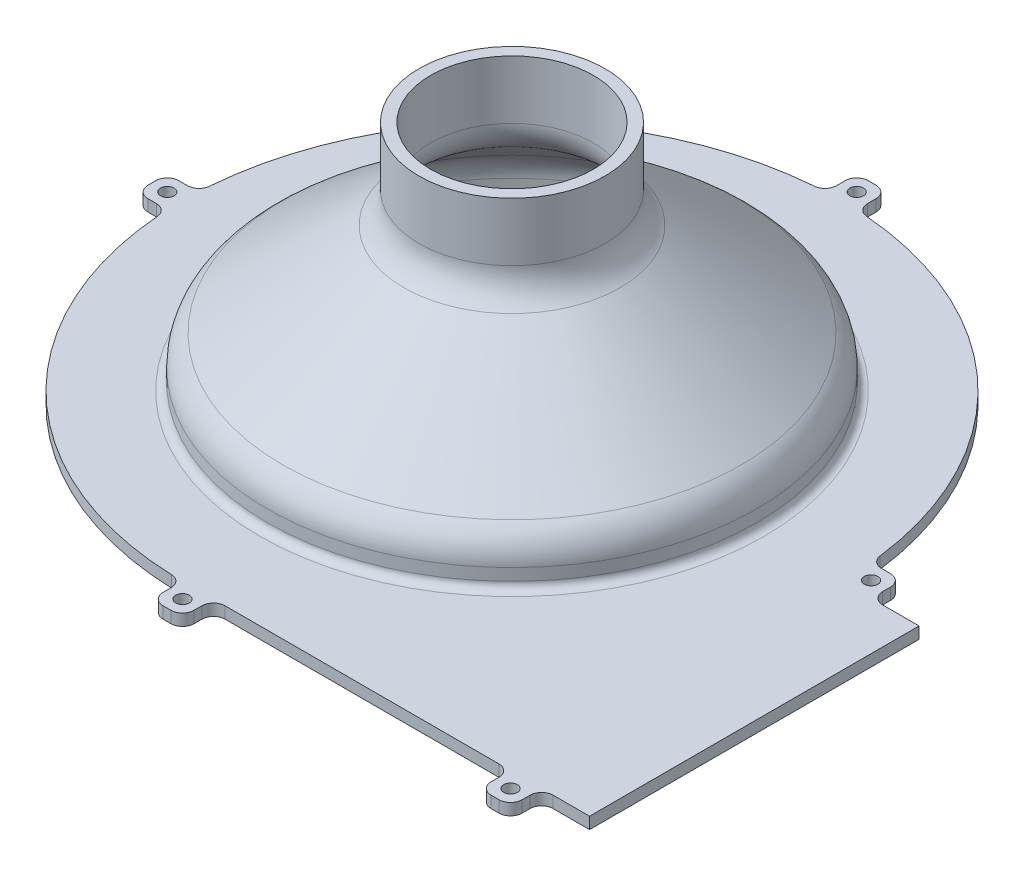
SolidWorks part; units mm, degrees
ref_plane "Front Plane" through (0, 0, 0) normal (0, 0, 1) x (1, 0, 0)
ref_plane "Top Plane" through (0, 0, 0) normal (0, 1, 0) x (1, 0, 0)
ref_plane "Right Plane" through (0, 0, 0) normal (1, 0, 0) x (0, 0, -1)
sketch "Sketch2" plane through (0, 0, 0) normal (0, 1, 0) x (1, 0, 0)
  line L0 (85, 0) -> (85, -85) construction
  line L1 (0, -85) -> (105, -85)
  line L3 (85, 0) -> (105, 0)
  line L4 (105, -85) -> (105, 0)
  arc A0 (85, 0) -> (0, -85) centre (0, 0) ccw
  circle A1 centre (0, 0) radius 60
  dimension "D1" = 170
  dimension "D4" = 120
  dimension "D3" = 20
extrude "Boss-Extrude1" add sketch "Sketch2" along normal blind 3
sketch "Sketch3" plane through (0, 3, 0) normal (0, 1, 0) x (1, 0, 0)
  circle A2 centre (0, 0) radius 60 construction
  circle A3 centre (0, 0) radius 60
  circle A4 centre (0, 0) radius 63
  dimension "D1" = 3
extrude "Boss-Extrude2" add sketch "Sketch3" along normal blind 10
sketch "Sketch6" plane through (0, 0, 0) normal (1, 0, 0) x (0, 0, -1)
  line L0 (-63, 13) -> (-24, 43)
  line L1 (-24, 43) -> (-21, 43)
  line L2 (-21, 43) -> (-60, 13)
  line L3 (63, 13) -> (-63, 13) construction
  line L4 (-63, 13) -> (-60, 13)
  line L5 (0, 0) -> (0, 43) construction
  line L6 (-85, 0) -> (85, 0) construction
  line L7 (-21, 43) -> (0, 43) construction
  dimension "D1" = 3
  dimension "D2" = 30
  dimension "D3" = 24
revolve "Revolve1" add sketch "Sketch6" angle 360 about L5
sketch "Sketch7" plane through (0, 43, 0) normal (0, 1, 0) x (1, 0, 0)
  circle A0 centre (0, 0) radius 24
  circle A1 centre (0, 0) radius 21
  circle A2 centre (0, 0) radius 21 construction
  circle A3 centre (0, 0) radius 24 construction
  point P5 (0.2049, -0.2216)
extrude "Boss-Extrude3" add sketch "Sketch7" along normal blind 20
fillet "Fillet1" radius 10 4 edges at (0, 43, -21) (0, 13, -60) (0, 13, 63) (0, 43, 24)
fillet "Fillet2" radius 2 1 edges at (0, 3, 63)
sketch "Sketch8" plane through (0, 0, 0) normal (0, -1, 0) x (1, 0, 0)
  line L21 (105, 0) -> (85, 0) construction
  line L22 (92.6227, 0) -> (84.6227, 0)
  line L23 (92.6227, 0) -> (92.6227, -8)
  line L24 (92.6227, -8) -> (84.6227, -8)
  line L25 (84.6227, 0) -> (84.6227, -8)
  line L26 (88.6227, 0) -> (88.6227, -8) construction
  line L27 (0, 85) -> (105, 85) construction
  line L28 (92.6227, 85) -> (84.6227, 85)
  line L29 (92.6227, 85) -> (92.6227, 93)
  line L30 (92.6227, 93) -> (84.6227, 93)
  line L31 (84.6227, 85) -> (84.6227, 93)
  line L32 (88.6227, 93) -> (88.6227, 85) construction
  line L33 (-88.9058, 4) -> (-88.9058, -4) construction
  line L34 (-84.9058, 4) -> (-92.9058, 4)
  line L35 (-84.9058, 4) -> (-84.9058, -4)
  line L36 (-84.9058, -4) -> (-92.9058, -4)
  line L37 (-92.9058, 4) -> (-92.9058, -4)
  line L38 (0, -84.9058) -> (0, -92.9058) construction
  line L39 (-4, -84.9058) -> (4, -84.9058)
  line L40 (-4, -84.9058) -> (-4, -92.9058)
  line L41 (-4, -92.9058) -> (4, -92.9058)
  line L42 (4, -84.9058) -> (4, -92.9058)
  line L43 (4, 93) -> (4, 85) construction
  line L44 (0, 85) -> (8, 85)
  line L45 (0, 85) -> (0, 93)
  line L46 (0, 93) -> (8, 93)
  line L47 (8, 85) -> (8, 93)
  arc A23 (0, 85) -> (85, 0) centre (0, 0) ccw construction
  circle A24 centre (88.6227, -4) radius 1.75
  circle A25 centre (88.6227, 89) radius 1.75
  circle A26 centre (-88.9058, 0) radius 1.75
  circle A27 centre (0, -88.9058) radius 1.75
  circle A28 centre (4, 89) radius 1.75
  dimension "D3" = 3.5
  dimension "D5" = 3.5
  dimension "D8" = 3.5
  dimension "D11" = 3.5
  dimension "D13" = 3.5
  dimension "D1" = 8
  dimension "D2" = 8
  dimension "D4" = 8
  dimension "D6" = 8
  dimension "D7" = 8
  dimension "D9" = 8
  dimension "D10" = 8
  dimension "D12" = 8
extrude "Boss-Extrude4" add sketch "Sketch8" against normal up to surface (3 mm away) up to face at (0, 3, 65)
fillet "Fillet3" radius 3 19 edges at (92.6227, 1.5, 0) (84.6227, 1.5, -8) (92.6227, 1.5, -8) (92.6227, 1.5, 85) (92.6227, 1.5, 93) (84.6227, 1.5, 93) (84.6227, 1.5, 85) (8, 1.5, 85) (8, 1.5, 93) (0, 1.5, 93) (0, 1.5, 85) (-84.9058, 1.5, 4) (-92.9058, 1.5, 4) (-92.9058, 1.5, -4) (-84.9058, 1.5, -4) (-4, 1.5, -92.9058) (4, 1.5, -92.9058) (4, 1.5, -84.9058) (-4, 1.5, -84.9058)
equation "\"LoftHeight\"= 30"
